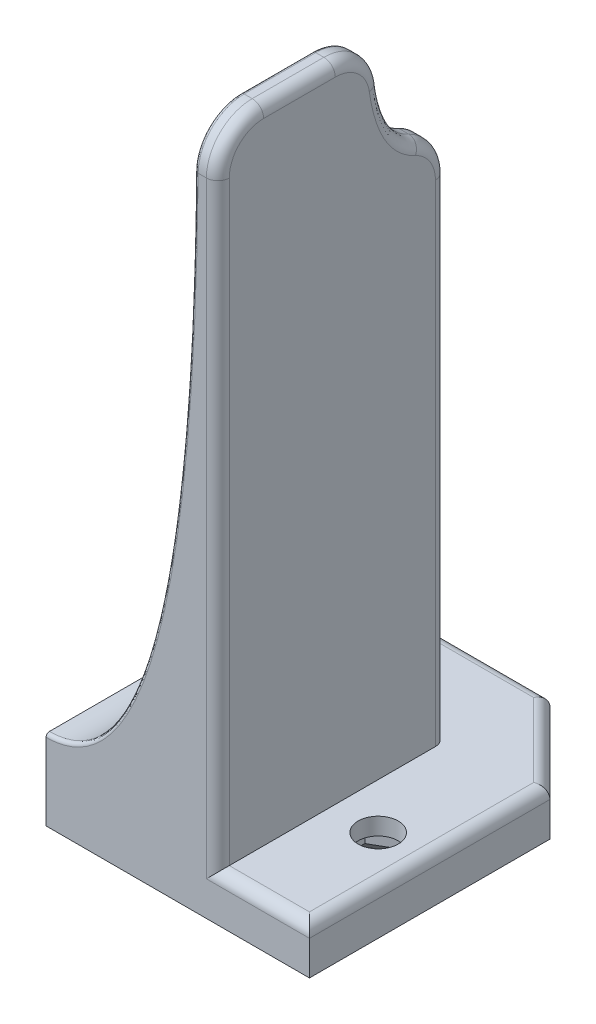
SolidWorks part; units mm, degrees
ref_plane "Front Plane" through (0, 0, 0) normal (0, 0, 1) x (1, 0, 0)
ref_plane "Top Plane" through (0, 0, 0) normal (0, 1, 0) x (1, 0, 0)
ref_plane "Right Plane" through (0, 0, 0) normal (1, 0, 0) x (0, 0, -1)
sketch "Sketch1" plane through (0, 0, 0) normal (0, 0, 1) x (1, 0, 0)
  line L0 (0, 0) -> (15, 0)
  line L1 (15, 0) -> (15, 60)
  line L2 (15, 60) -> (13, 60)
  line L3 (0, 7) -> (13, 7) construction
  line L4 (13, 7) -> (13, 60) construction
  line L5 (0, 0) -> (0, 7)
  spline S0 degree 2 poles (0, 7) (13, 7) (13, 60) knots 0 0 0 1 1 1
  dimension "D1" = 2
  dimension "D2" = 60
  dimension "D3" = 15
  dimension "D4" = 7
extrude "Boss-Extrude1" add sketch "Sketch1" along normal blind 20
sketch "Sketch2" plane through (0, 0, 0) normal (1, 0, 0) x (0, 0, -1)
  line L0 (-20, 60) -> (0, 60) construction
  line L1 (-6, 60) -> (-6, 50) construction
  line L2 (-6, 50) -> (0, 50) construction
  line L3 (0, 7) -> (0, 60) construction
  line L4 (0, 50) -> (0, 60)
  line L5 (0, 60) -> (-6, 60)
  spline S0 degree 2 poles (-6, 60) (-6, 50) (0, 50) knots 0 0 0 1 1 1
  dimension "D1" = 10
  dimension "D2" = 6
extrude "Cut-Extrude2" cut sketch "Sketch2" against normal through all and the other way through all
sketch "Sketch3" plane through (0, 0, 0) normal (0, -1, 0) x (1, 0, 0)
  line L0 (0, 0) -> (15, 0) construction
  line L1 (0, 20) -> (23, 20)
  line L2 (0, 20) -> (0, -8)
  line L3 (0, -8) -> (23, -8)
  line L4 (23, 20) -> (23, -8)
  line L5 (15, 20) -> (15, 0) construction
  dimension "D1" = 8
  dimension "D2" = 8
extrude "Boss-Extrude2" add sketch "Sketch3" against normal blind 4
chamfer "Chamfer1" distance 7 angle 45 1 edges at (23, 2, -8)
sketch "Sketch4" plane through (0, 0, 0) normal (0, -1, 0) x (1, 0, 0)
  line L0 (15, 0) -> (15, 20) construction
  line L1 (4.3246, -4) -> (5.9123, -6.75)
  line L2 (5.9123, -6.75) -> (9.0877, -6.75)
  line L3 (9.0877, -6.75) -> (10.6754, -4)
  line L4 (10.6754, -4) -> (9.0877, -1.25)
  line L5 (9.0877, -1.25) -> (5.9123, -1.25)
  line L6 (5.9123, -1.25) -> (4.3246, -4)
  line L7 (19, 6.8246) -> (21.75, 8.4123)
  line L8 (21.75, 8.4123) -> (21.75, 11.5877)
  line L9 (21.75, 11.5877) -> (19, 13.1754)
  line L10 (19, 13.1754) -> (16.25, 11.5877)
  line L11 (16.25, 11.5877) -> (16.25, 8.4123)
  line L12 (16.25, 8.4123) -> (19, 6.8246)
  line L13 (15, 0) -> (15, 20) construction
  line L14 (15, 0) -> (0, 0) construction
  line L15 (15, 0) -> (0, 0) construction
  line L17 (7.5, 0) -> (7.5, -8) construction
  line L18 (0, -8) -> (16, -8) construction
  line L19 (15, 10) -> (23, 10) construction
  line L20 (23, -1) -> (23, 20) construction
  circle A0 centre (7.5, -4) radius 2.75 construction
  circle A1 centre (19, 10) radius 2.75 construction
  point P26 (7.5, -4)
  point P31 (19, 10)
  dimension "D1" = 5.5
  dimension "D2" = 5.5
extrude "Cut-Extrude3" cut sketch "Sketch4" against normal blind 2.5
sketch "Sketch5" plane through (0, 0, 0) normal (0, -1, 0) x (1, 0, 0)
  circle A0 centre (7.5, -4) radius 1.75
  circle A1 centre (19, 10) radius 1.75
  dimension "D1" = 3.5
extrude "Cut-Extrude4" cut sketch "Sketch5" against normal through all
chamfer "Chamfer2" distance 1 angle 45 12 edges at (7.5, 0, -6.75) (9.8816, 0, -5.375) (9.8816, 0, -2.625) (7.5, 0, -1.25) (5.1184, 0, -2.625) (5.1184, 0, -5.375) (21.75, 0, 10) (20.375, 0, 12.3816) (17.625, 0, 12.3816) (16.25, 0, 10) (17.625, 0, 7.6184) (20.375, 0, 7.6184)
fillet "Fillet1" radius 4 3 edges at (14, 60, 20) (14, 60, 6) (13.9359, 50, 0)
fillet "Fillet2" radius 1 7 edges at (15, 30, 20) (15, 58.8284, 18.8284) (15, 25.4201, 0) (15, 48.9952, 0.6302) (15, 59.0193, 7.1202) (15, 60, 12.8719)
fillet "Fillet3" radius 1 5 edges at (0, 4, -4) (18.5, 4, 20) (23, 4, 9.5) (19.5, 4, -4.5) (8, 4, -8)
fillet "Fillet4" radius 0.3 7 edges at (12.8318, 48.6279, 0.4218) (12.9153, 51.7906, 4.0035) (12.9991, 59.1235, 7.2451) (13, 60, 12.8719) (12.9974, 58.4987, 19.1235)
